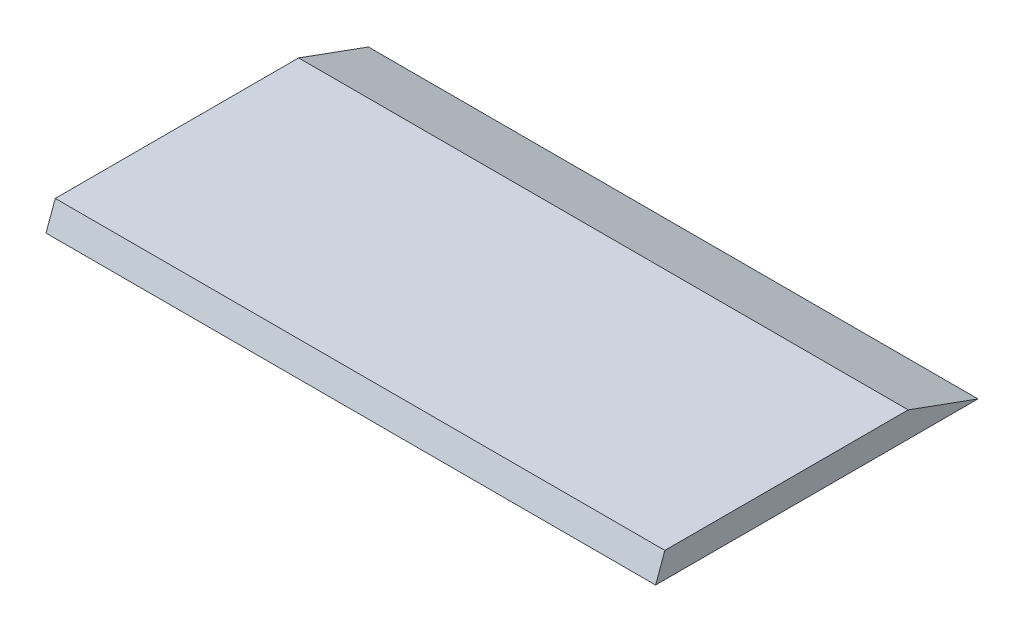
SolidWorks part; units mm, degrees
ref_plane "Front Plane" through (0, 0, 0) normal (0, 0, 1) x (1, 0, 0)
ref_plane "Top Plane" through (0, 0, 0) normal (0, 1, 0) x (1, 0, 0)
ref_plane "Right Plane" through (0, 0, 0) normal (1, 0, 0) x (0, 0, -1)
sketch "Sketch1" plane through (0, 0, 0) normal (0, 1, 0) x (1, 0, 0)
  line L1 (0, 0) -> (240, 0)
  line L2 (0, 0) -> (0, 126.92)
  line L3 (0, 126.92) -> (240, 126.92)
  line L4 (240, 0) -> (240, 126.92)
  dimension "D1" = 240
  dimension "D2" = 126.92
extrude "Boss-Extrude1" add sketch "Sketch1" along normal blind 10
chamfer "Chamfer1" distance 10 angle 70 1 edges at (120, 10, -126.92) first distance on face at (120, 5, -126.92)
chamfer "Chamfer3" distance 10 angle 20 1 edges at (120, 10, 0) first distance on face at (120, 5, 0)
